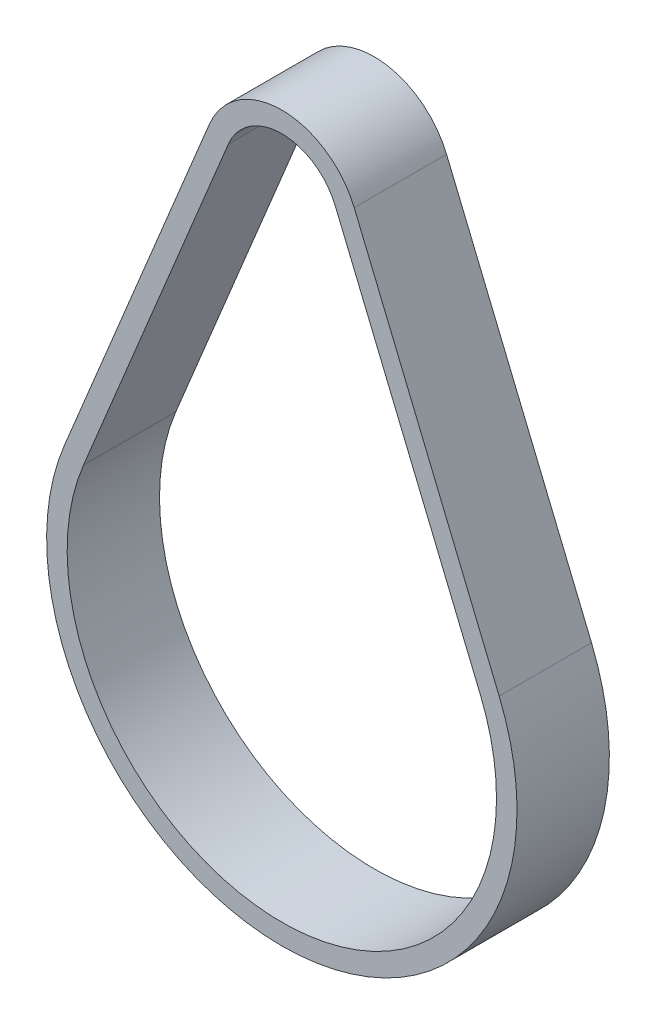
SolidWorks part; units mm, degrees
material "Rubber"
ref_plane "Front Plane" through (0, 0, 0) normal (0, 0, 1) x (1, 0, 0)
ref_plane "Top Plane" through (0, 0, 0) normal (0, 1, 0) x (1, 0, 0)
ref_plane "Right Plane" through (0, 0, 0) normal (1, 0, 0) x (0, 0, -1)
sketch "Sketch1" plane through (0, 0, 0) normal (0, 0, 1) x (1, 0, 0)
  line L0 (-7.0556, 2.9175) -> (-21.1806, -31.2417)
  line L1 (7.0556, 2.9175) -> (21.1806, -31.2417)
  arc A0 (7.0556, 2.9175) -> (-7.0556, 2.9175) centre (0, 0) ccw
  arc A1 (-21.1806, -31.2417) -> (21.1806, -31.2417) centre (0, -40) ccw
  point P9 (0, 0)
  point P10 (6.3111, -6.0463)
  dimension "D1" = 15.27
  dimension "D2" = 45.84
  dimension "D3" = 40
extrude "Extrude-Thin1" add sketch "Sketch1" along normal mid plane 9 thin thin type one direction reverse wall 2
